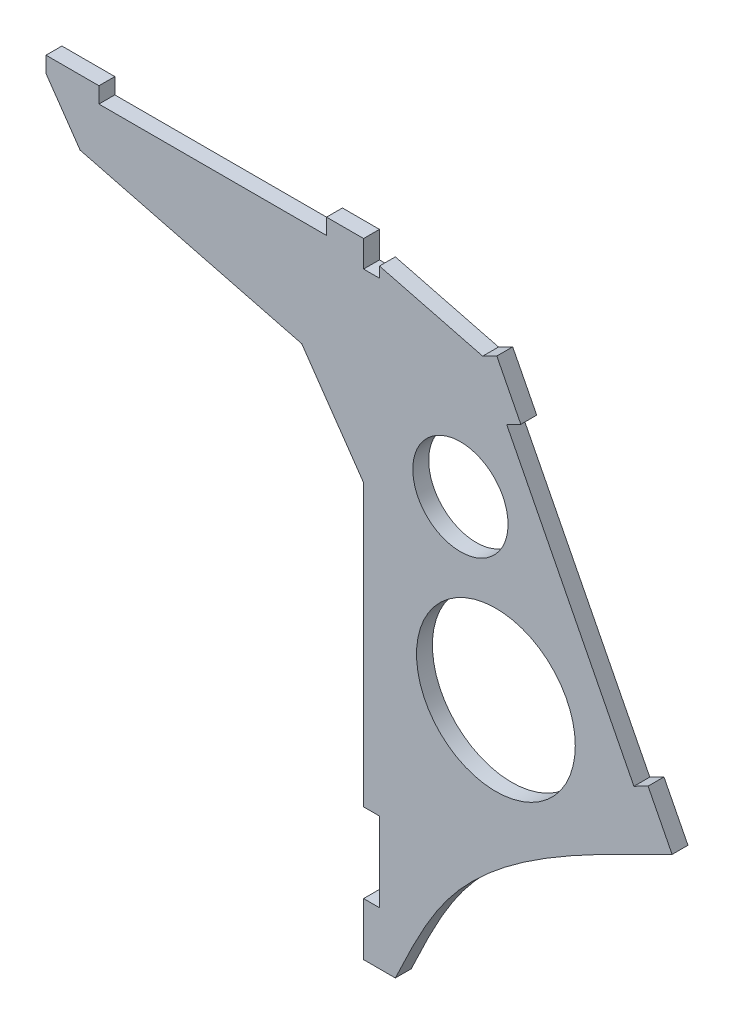
SolidWorks part; units mm, degrees
material "201 Stal nierdzewna odprężona (SS)"
ref_plane "Płaszczyzna przednia" through (0, 0, 0) normal (0, 0, 1) x (1, 0, 0)
ref_plane "Płaszczyzna górna" through (0, 0, 0) normal (0, 1, 0) x (1, 0, 0)
ref_plane "Płaszczyzna prawa" through (0, 0, 0) normal (1, 0, 0) x (0, 0, -1)
sketch "Szkic1" plane through (0, 0, 0) normal (0, 0, 1) x (1, 0, 0)
  line L0 (-61.5433, -53.4415) -> (-19.665, -64.1797)
  line L1 (-19.665, -64.1797) -> (-7.9858, -81.0758)
  line L30 (-67.9858, -44.1214) -> (-61.5433, -53.4415)
  line L31 (-4.9858, -134.1214) -> (-7.9858, -134.1214)
  line L32 (-67.9858, -41.1214) -> (-57.9858, -41.1214)
  line L33 (-14.9858, -44.1214) -> (-14.9858, -41.1214)
  line L34 (-14.9858, -41.1214) -> (-7.9858, -41.1214)
  line L35 (-67.9858, -44.1214) -> (-67.9858, -41.1214)
  line L36 (-57.9858, -41.1214) -> (-57.9858, -44.1214)
  line L37 (-57.9858, -44.1214) -> (-14.9858, -44.1214)
  line L38 (-4.9858, -46.1214) -> (-4.9858, -44.1214)
  line L39 (-4.9858, -44.1214) -> (14.5141, -49.1214)
  line L40 (-7.9858, -81.0758) -> (-7.9858, -134.1214)
  line L41 (19.054, -58.0314) -> (43.0933, -105.2113)
  line L42 (43.0933, -105.2113) -> (45.7663, -103.8493)
  line L43 (47.6332, -114.1214) -> (50.3062, -112.7594)
  line L44 (45.7663, -103.8493) -> (50.3062, -112.7594)
  line L45 (14.5141, -49.1214) -> (17.1871, -47.7594)
  line L46 (17.1871, -47.7594) -> (21.727, -56.6695)
  line L47 (19.054, -58.0314) -> (21.727, -56.6695)
  line L48 (-4.9858, -149.1214) -> (-4.9858, -134.1214)
  line L49 (-7.9858, -149.1214) -> (-7.9858, -159.1214)
  line L50 (-1.9858, -159.1214) -> (-7.9858, -159.1214)
  line L51 (-4.9858, -149.1214) -> (-7.9858, -149.1214)
  line L52 (-4.9858, -46.1214) -> (-7.9858, -46.1214)
  line L53 (-7.9858, -46.1214) -> (-7.9858, -41.1214)
  circle A20 centre (17.0142, -104.1214) radius 15
  circle A21 centre (10.3105, -74.2267) radius 9
  spline S0 degree 3 poles (-1.9858, -159.1214) (0.831, -153.1266) (10.7023, -132.1185) (32.2408, -121.6224) (47.6332, -114.1214) knots 0 0 0 0 0.285353 1 1 1 1
  dimension "D1" = 10
  dimension "D4" = 18
  dimension "D2" = 43
  dimension "D3" = 7
extrude "Dodanie-wyciągnięcie1" add sketch "Szkic1" along normal blind 3
